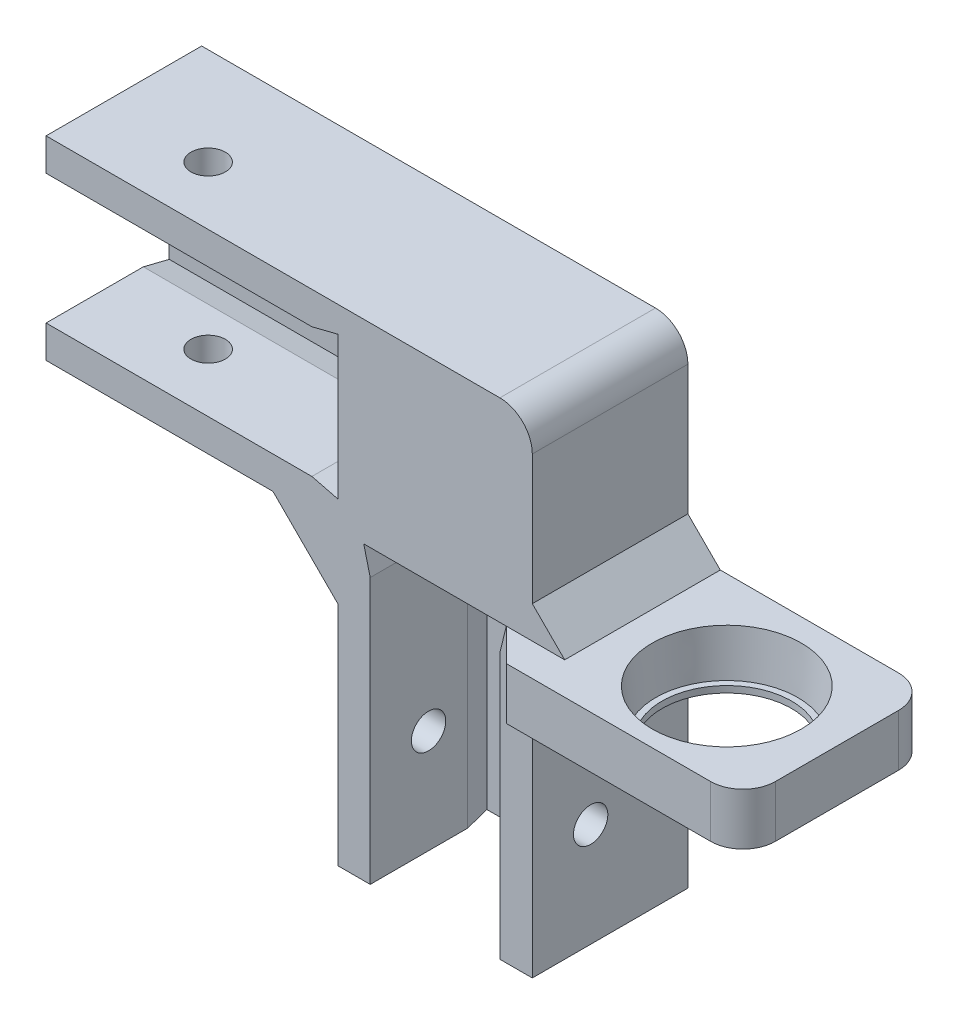
SolidWorks part; units mm, degrees
ref_plane "Front Plane" through (0, 0, 0) normal (0, 0, 1) x (1, 0, 0)
ref_plane "Top Plane" through (0, 0, 0) normal (0, 1, 0) x (1, 0, 0)
ref_plane "Right Plane" through (0, 0, 0) normal (1, 0, 0) x (0, 0, -1)
sketch "Sketch1" plane through (0, 0, 0) normal (0, 0, 1) x (1, 0, 0)
  line L1 (0, 0) -> (75, 0)
  line L2 (0, 0) -> (0, 75)
  line L3 (0, 75) -> (75, 75)
  line L4 (75, 0) -> (75, 75)
  dimension "D1" = 75
  dimension "D2" = 75
extrude "Boss-Extrude1" add sketch "Sketch1" along normal blind 24
sketch "Sketch2" plane through (0, 0, 0) normal (0, -1, 0) x (1, 0, 0)
  line L1 (25, 24) -> (5, 24)
  line L2 (25, 24) -> (25, 5)
  line L3 (25, 5) -> (5, 5)
  line L4 (5, 24) -> (5, 5)
  line L6 (0, 0) -> (75, 0) construction
  line L7 (0, 24) -> (75, 24) construction
  line L8 (0, 24) -> (0, 0) construction
  dimension "D1" = 5
  dimension "D2" = 5
  dimension "D3" = 20
extrude "Cut-Extrude1" cut sketch "Sketch2" against normal blind 45
sketch "Sketch3" plane through (75, 0, 0) normal (1, 0, 0) x (0, 0, -1)
  line L1 (-24, 50) -> (-5, 50)
  line L2 (-24, 50) -> (-24, 70)
  line L3 (-24, 70) -> (-5, 70)
  line L4 (-5, 50) -> (-5, 70)
  line L5 (-24, 75) -> (0, 75) construction
  line L6 (-24, 0) -> (-24, 75) construction
  line L9 (0, 0) -> (0, 75) construction
  dimension "D1" = 5
  dimension "D2" = 20
  dimension "D3" = 5
extrude "Cut-Extrude2" cut sketch "Sketch3" against normal blind 45
sketch "Sketch4" plane through (0, 0, 24) normal (0, 0, 1) x (1, 0, 0)
  line L0 (30, 50) -> (75, 50) construction
  line L1 (75, 0) -> (30, 0)
  line L2 (75, 0) -> (75, 45)
  line L3 (75, 45) -> (30, 45)
  line L4 (30, 0) -> (30, 45)
  line L5 (25, 45) -> (25, 0) construction
  dimension "D1" = 5
  dimension "D2" = 5
extrude "Cut-Extrude3" cut sketch "Sketch4" against normal through all both and the other way through all
fillet "Fillet1" radius 5 1 edges at (0, 75, 12)
chamfer "Chamfer1" distance 10 angle 45 1 edges at (30, 45, 12)
sketch "Sketch5" plane through (0, 0, 0) normal (-1, 0, 0) x (0, 0, 1)
  line L1 (29, 45) -> (0, 45)
  line L2 (29, 45) -> (29, 37)
  line L3 (29, 37) -> (0, 37)
  line L4 (0, 45) -> (0, 37)
  line L5 (5, 45) -> (24, 45) construction
  line L6 (0, 70) -> (0, 0) construction
  dimension "D1" = 8
  dimension "D2" = 29
extrude "Boss-Extrude2" add sketch "Sketch5" along normal blind 37.5
sketch "Sketch6" plane through (0, 45, 0) normal (0, 1, 0) x (1, 0, 0)
  circle A0 centre (-21, -15) radius 11.5
  dimension "D1" = 23
extrude "Cut-Extrude4" cut sketch "Sketch6" against normal blind 7
fillet "Fillet2" radius 5 2 edges at (-37.5, 41, 29) (-37.5, 41, 0)
chamfer "Chamfer3" distance 5 angle 45 2 edges at (0, 45, 12) (0, 37, 12)
sketch "Sketch7" plane through (0, 45, 0) normal (0, -1, 0) x (1, 0, 0)
  line L0 (75, 0) -> (75, 24) construction
  line L1 (40, 24) -> (75, 24) construction
  circle A0 centre (59, 15) radius 2.65
  dimension "D1" = 5.3
  dimension "D2" = 16
  dimension "D3" = 9
extrude "Cut-Extrude5" cut sketch "Sketch7" against normal through all both and the other way through all
sketch "Sketch8" plane through (30, 0, 0) normal (1, 0, 0) x (0, 0, -1)
  line L0 (0, 0) -> (-24, 0) construction
  line L1 (-24, 0) -> (-24, 35) construction
  circle A0 centre (-15, 16) radius 2.65
  dimension "D1" = 5.3
  dimension "D2" = 16
  dimension "D3" = 9
extrude "Cut-Extrude6" cut sketch "Sketch8" against normal through all both and the other way through all
sketch "Sketch9" plane through (0, 0, 5) normal (0, 0, 1) x (1, 0, 0)
  line L0 (5, 0) -> (25, 0) construction
  line L1 (25, 45) -> (25, 0) construction
  circle A0 centre (15, 22.5) radius 2.65
  dimension "D1" = 5.3
  dimension "D2" = 22.5
  dimension "D3" = 10
extrude "Cut-Extrude7" cut sketch "Sketch9" against normal blind 10
sketch "Sketch10" plane through (0, 0, 5) normal (0, 0, 1) x (1, 0, 0)
  line L0 (30, 70) -> (75, 70) construction
  line L1 (75, 50) -> (75, 70) construction
  circle A0 centre (52.5, 60) radius 2.65
  dimension "D1" = 5.3
  dimension "D2" = 10
  dimension "D3" = 22.5
extrude "Cut-Extrude8" cut sketch "Sketch10" against normal blind 10
sketch "Sketch11" plane through (0, 0, 24) normal (0, 0, 1) x (1, 0, 0)
  line L0 (34, 70) -> (30, 71)
  line L1 (30, 70) -> (75, 70) construction
  line L2 (30, 71) -> (30, 70)
  line L3 (30, 70) -> (34, 70)
  line L4 (30, 50) -> (34, 50)
  line L5 (30, 50) -> (75, 50) construction
  line L6 (34, 50) -> (30, 49)
  line L7 (30, 49) -> (30, 50)
  line L10 (26, 45) -> (25, 41)
  line L14 (25, 45) -> (25, 0) construction
  line L16 (5, 45) -> (4, 45)
  line L17 (-5, 45) -> (0, 45) construction
  line L18 (4, 45) -> (5, 41)
  line L20 (5, 41) -> (5, 45)
  line L21 (25, 45) -> (26, 45)
  line L22 (25, 41) -> (25, 45)
  dimension "D1" = 4
  dimension "D2" = 1
  dimension "D3" = 1
  dimension "D4" = 4
  dimension "D5" = 1
  dimension "D6" = 1
  dimension "D7" = 4
  dimension "D8" = 4
extrude "Cut-Extrude12" cut sketch "Sketch11" against normal up to surface (19 mm away) up to face at (17.65, 22.5, 5)
sketch "Sketch12" plane through (0, 0, 0) normal (0, -1, 0) x (1, 0, 0)
  line L0 (5, 5) -> (4, 5)
  line L1 (4, 5) -> (5, 9)
  line L2 (5, 24) -> (5, 5) construction
  line L3 (5, 9) -> (5, 5)
  line L4 (25, 5) -> (26, 5)
  line L5 (26, 5) -> (25, 9)
  line L6 (25, 5) -> (25, 24) construction
  line L7 (25, 9) -> (25, 5)
  dimension "D1" = 4
  dimension "D2" = 4
  dimension "D3" = 1
  dimension "D4" = 1
extrude "Cut-Extrude13" cut sketch "Sketch12" against normal up to surface (45 mm away) up to face at (15, 45, 14.5)
sketch "Sketch13" plane through (75, 0, 0) normal (1, 0, 0) x (0, 0, -1)
  line L0 (-5, 50) -> (-5, 49)
  line L1 (-5, 49) -> (-9, 50)
  line L2 (-24, 50) -> (-5, 50) construction
  line L3 (-9, 50) -> (-5, 50)
  line L4 (-5, 70) -> (-5, 71)
  line L5 (-5, 71) -> (-9, 70)
  line L6 (-5, 70) -> (-24, 70) construction
  line L7 (-9, 70) -> (-5, 70)
  dimension "D1" = 1
  dimension "D2" = 4
  dimension "D3" = 4
  dimension "D4" = 1
extrude "Cut-Extrude14" cut sketch "Sketch13" against normal up to surface (45 mm away) up to face at (30, 60, 14.5)
sketch "Sketch14" plane through (0, 38, 0) normal (0, 1, 0) x (1, 0, 0)
  circle A0 centre (-21, -15) radius 10
  dimension "D1" = 20
extrude "Cut-Extrude15" cut sketch "Sketch14" against normal blind 10
chamfer "Chamfer5" distance 4 angle 45 1 edges at (0, 41, 24)
chamfer "Chamfer6" distance 1 angle 45 1 edges at (0, 41, 29)
chamfer "Chamfer8" distance 7 angle 4.5 1 edges at (-32.5, 38, 15) first distance on face at (-32.5, 38, 15)
mirror "Mirror1" about plane through (75, 0, 24) normal (-1, 0, 0) of bodies 117 108
delete or keep bodies "Body-Delete/Keep 1" type delete bodies bodies 117
